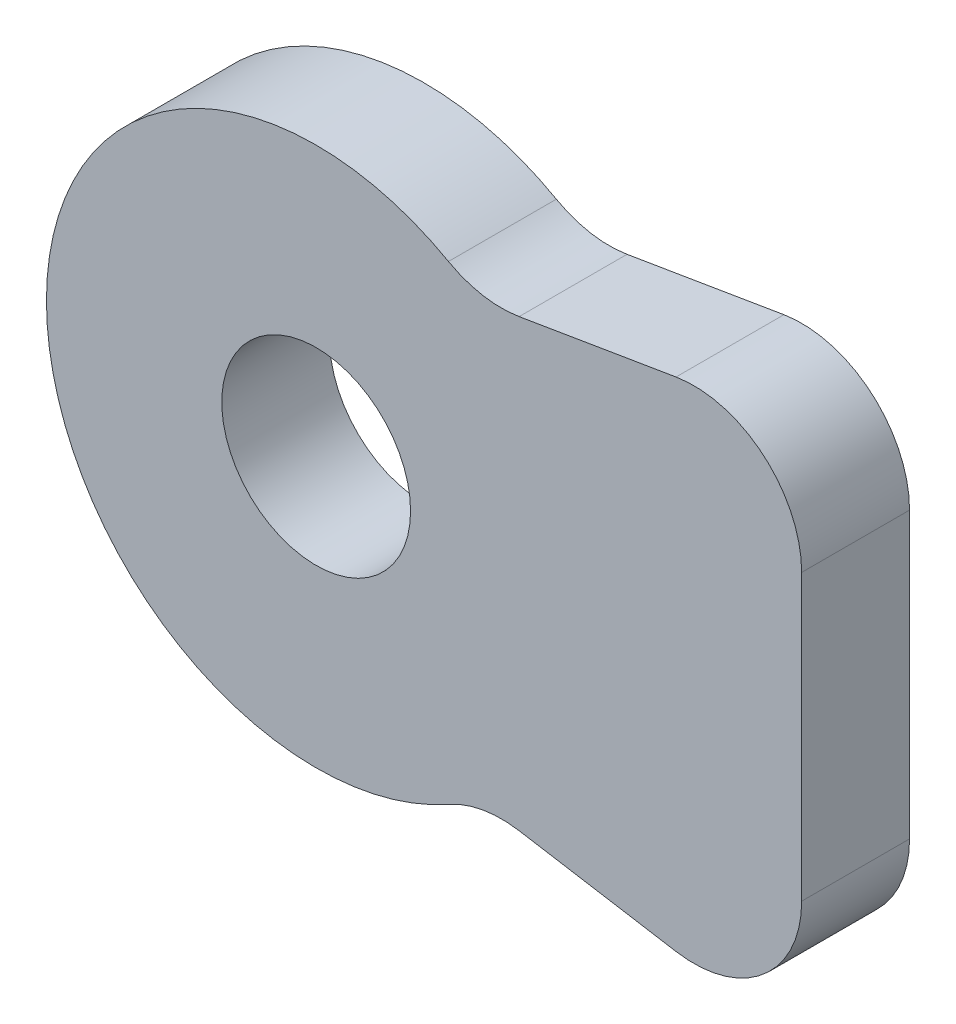
SolidWorks part; units mm, degrees
ref_plane "Front" through (0, 0, 0) normal (0, 0, 1) x (1, 0, 0)
ref_plane "Top" through (0, 0, 0) normal (0, 1, 0) x (1, 0, 0)
ref_plane "Right" through (0, 0, 0) normal (1, 0, 0) x (0, 0, -1)
sketch "Esquisse1" plane through (0, 0, 0) normal (0, 0, 1) x (1, 0, 0)
  circle A0 centre (0, 0) radius 1.75
  circle A1 centre (0, 0) radius 5
  dimension "D1" = 3.5
  dimension "D2" = 10
extrude "Boss.-Extru.1" add sketch "Esquisse1" along normal blind 2
sketch "Esquisse2" plane through (0, 0, 2) normal (0, 0, 1) x (1, 0, 0)
  line L0 (0, 0) -> (9, 0) construction
  line L1 (9, 5) -> (9, -5)
  line L2 (9, -5) -> (3, -4)
  line L3 (3, -4) -> (3, 4)
  line L4 (9, 5) -> (3, 4)
  circle A1 centre (0, 0) radius 5 construction
  point P9 (3, 0)
  dimension "D1" = 10
  dimension "D2" = 9
  dimension "D3" = 6
extrude "Boss.-Extru.2" add sketch "Esquisse2" against normal blind 2
fillet "Congé1" radius 2 4 edges at (3, -4, 1) (3, 4, 1) (9, -5, 1) (9, 5, 1)
